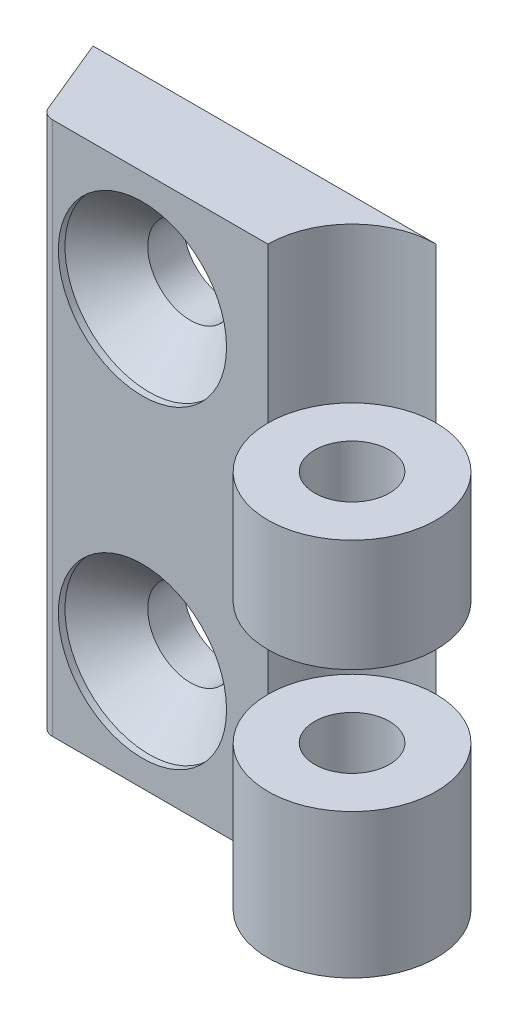
SolidWorks part; units mm, degrees
ref_plane "Front Plane" through (0, 0, 0) normal (0, 0, 1) x (1, 0, 0)
ref_plane "Top Plane" through (0, 0, 0) normal (0, 1, 0) x (1, 0, 0)
ref_plane "Right Plane" through (0, 0, 0) normal (1, 0, 0) x (0, 0, -1)
sketch "Sketch1" plane through (0, 0, 0) normal (0, 1, 0) x (1, 0, 0)
  line L0 (0, 6.3) -> (-25.7, 6.3)
  line L2 (-22.4338, 0) -> (-6.3, 0)
  line L3 (-23.1032, 0) -> (-23.1032, 0.2571) construction
  line L4 (-23.3584, 0.6189) -> (-25.7, 6.3)
  line L5 (-25.7, 6.3) -> (-25.6544, 6.2163)
  arc A0 (-23.3584, 0.6189) -> (-22.4338, 0) centre (-22.4338, 1) ccw
  circle A1 centre (0, 0) radius 2.8
  circle A2 centre (0, 0) radius 6.3
  dimension "D1" = 1
  dimension "D2" = 12.6
  dimension "D3" = 6.3
  dimension "D4" = 25.7
extrude "Boss-Extrude1" add sketch "Sketch1" along normal blind 10.8 contours A2 L0 L2 | A2 L2 A1 | A2 A1 | L2 A2 A1 region at (-14.633, 0, -3.3433) region at (4.3288, 0, -4.3288)
extrude "Boss-Extrude2" add sketch "Sketch1<3>" along normal blind 40 contours A2 L0 L2 region at (-14.633, 0, -3.3433)
sketch "Sketch1<3>" plane through (0, 0, 0) normal (0, 1, 0) x (1, 0, 0) same geometry as "Sketch1"
extrude "Boss-Extrude5" add sketch "Sketch1<7>" along normal blind 8.4 from offset 20 contours L2 A2 A1 | A2 L2 A1 | A2 A1 region at (4.3288, 0, -4.3288)
sketch "Sketch1<7>" plane through (0, 0, 0) normal (0, 1, 0) x (1, 0, 0) same geometry as "Sketch1"
sketch "Sketch2" plane through (0, 0, 0) normal (0, 0, 1) x (1, 0, 0)
  line L0 (-25.7, 40) -> (-25.7, 0) construction
  line L1 (-25.7, 20) -> (7.0971, 20) construction
  circle A0 centre (-15.7, 31.75) radius 3.5
  circle A1 centre (-15.7, 31.75) radius 6
  circle A2 centre (-15.7, 8.25) radius 6
  circle A3 centre (-15.7, 8.25) radius 3.5
  dimension "D3" = 7
  dimension "D4" = 12
  dimension "D1" = 10
  dimension "D2" = 11.75
hole_wizard "CSK for M6 Countersunk Flat Head Screw1" positions "Sketch4" profile "Sketch3" countersink size "M6" standard "ISO" end condition through all
sketch "Sketch4" plane through (0, 0, 0) normal (0, 0, 1) x (1, 0, 0)
  point P0 (-15.7, 31.75)
  point P3 (-15.7, 8.25)
sketch "Sketch3" plane through (-15.7, 31.75, 0) normal (1, 0, 0) x (0, -1, 0)
  line L0 (0, 0) -> (0, 6.3)
  line L1 (0, 6.3) -> (3.2, 6.3)
  line L2 (3.2, 6.3) -> (3.2, 3.6)
  line L3 (3.2, 3.6) -> (6.3, 0.5)
  line L4 (6.3, 0.5) -> (6.3, 0)
  line L6 (6.3, 0) -> (0, 0)
  line L7 (-3.2, 3.6) -> (-6.3, 0.5) construction
  line L11 (0, -6.35) -> (0, 107.95) construction
  dimension "Thru Hole Dia." = 6.4
  dimension "Thru Hole Depth" = 6.3
  dimension "C'Sink Dia." = 12.6
  dimension "C'Sink Angle" = 90
  dimension "Head Clearance" = 0.5
